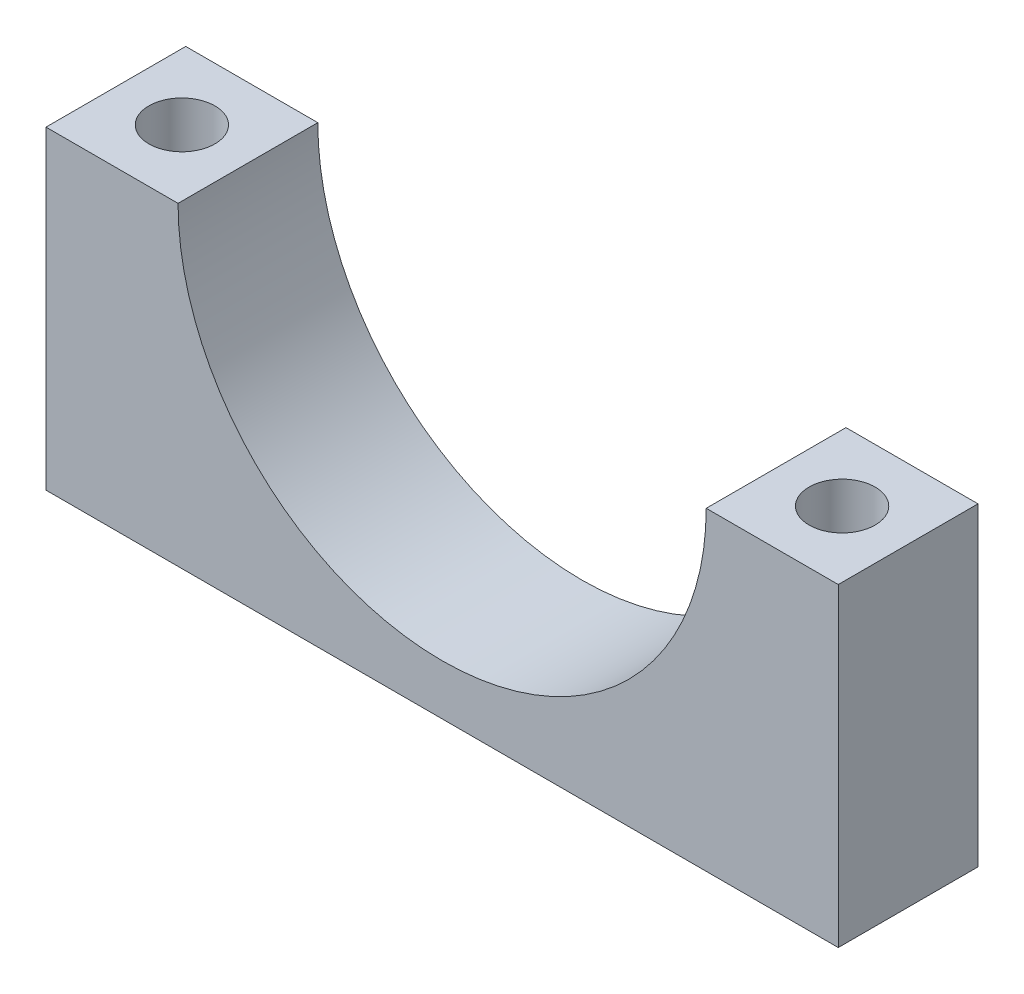
SolidWorks part; units mm, degrees
material "6061-T6 (SS)"
ref_plane "Front Plane" through (0, 0, 0) normal (0, 0, 1) x (1, 0, 0)
ref_plane "Top Plane" through (0, 0, 0) normal (0, 1, 0) x (1, 0, 0)
ref_plane "Right Plane" through (0, 0, 0) normal (1, 0, 0) x (0, 0, -1)
sketch "Sketch4" plane through (0, 0, 0) normal (0, 0, 1) x (1, 0, 0)
  line L0 (30, 14.2875) -> (36, 14.2875)
  line L1 (0, 0) -> (36, 0)
  line L2 (0, 0) -> (0, 14.2875)
  line L3 (0, 14.2875) -> (6, 14.2875)
  line L4 (36, 0) -> (36, 14.2875)
  arc A0 (6, 14.2875) -> (30, 14.2875) centre (18, 14.2875) ccw
  dimension "D3" = 24
  dimension "D4" = 18
  dimension "D1" = 14.2875
  dimension "D2" = 36
  dimension "D5" = 14.2875
extrude "Boss-Extrude1" add sketch "Sketch4" along normal blind 6.35
sketch "Sketch5" plane through (0, 14.2875, 0) normal (0, 1, 0) x (1, 0, 0)
  line L0 (6, 0) -> (0, 0) construction
  line L1 (0, -6.35) -> (0, 0) construction
  line L2 (36, -6.35) -> (36, 0) construction
  line L3 (36, 0) -> (30, 0) construction
  circle A0 centre (3, -3.175) radius 1.5
  circle A1 centre (33, -3.175) radius 1.5
  dimension "D3" = 3
  dimension "D6" = 3
  dimension "D1" = 3.175
  dimension "D2" = 3
  dimension "D4" = 3
  dimension "D5" = 3.175
extrude "Cut-Extrude1" cut sketch "Sketch5" against normal through all
